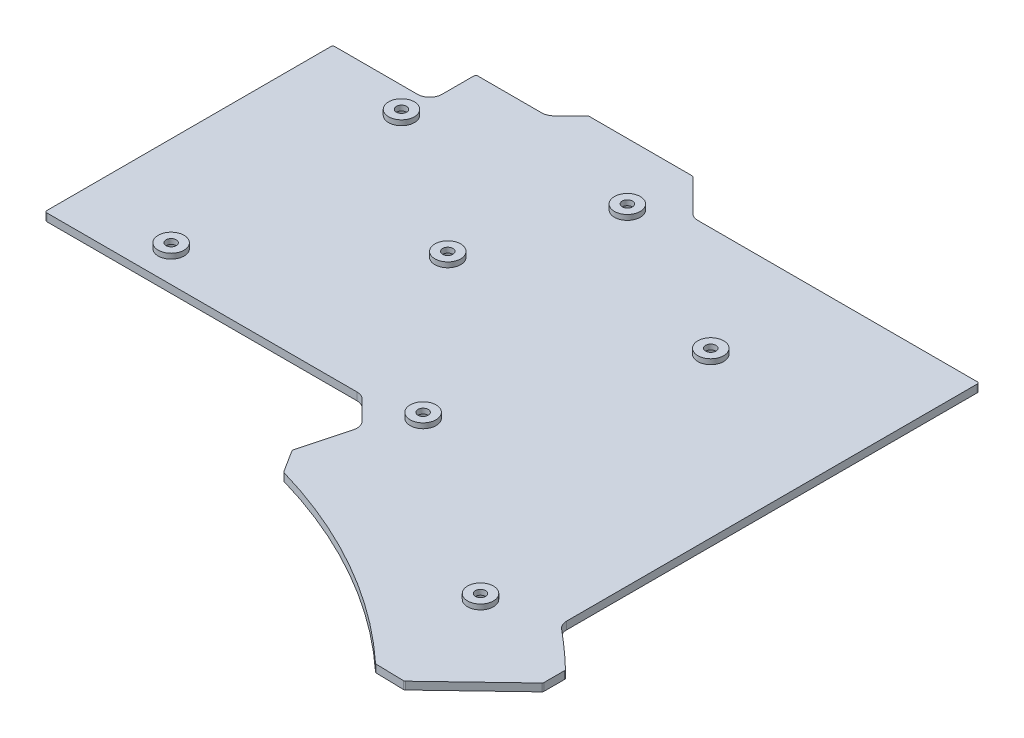
SolidWorks part; units mm, degrees
ref_plane "Piano frontale" through (0, 0, 0) normal (0, 0, 1) x (1, 0, 0)
ref_plane "Piano superiore" through (0, 0, 0) normal (0, 1, 0) x (1, 0, 0)
ref_plane "Piano destro" through (0, 0, 0) normal (1, 0, 0) x (0, 0, -1)
sketch "Schizzo1" plane through (0, 9.9972, 0) normal (0, -1, 0) x (1, 0, 0)
  line L17 (-61.586, 85.1099) -> (-61.586, 79.3099)
  line L18 (-61.586, 79.3099) -> (-48.9073, 79.3099)
  line L19 (-46.6445, 78.3726) -> (-43.5318, 75.2599)
  line L20 (-43.5318, 75.2599) -> (-22.9401, 75.2599)
  line L21 (-22.9401, 75.2599) -> (-16.8774, 81.3226)
  line L22 (-14.6146, 82.2599) -> (40.164, 82.2599)
  line L24 (40.164, 82.2599) -> (40.164, 162.6403)
  line L25 (48.3495, 171.436) -> (48.3495, 175.9915)
  line L26 (48.3495, 175.9915) -> (34.3416, 189.3477)
  line L27 (34.3416, 189.3477) -> (28.4404, 189.2072)
  line L28 (-13.0199, 165.7427) -> (-16.0073, 161.0261)
  line L29 (-16.0073, 161.0261) -> (-13.6027, 152.0521)
  line L30 (-14.4309, 148.9612) -> (-17.445, 145.9471)
  line L31 (-19.7077, 145.0099) -> (-80.536, 145.0099)
  line L32 (-80.536, 145.0099) -> (-80.536, 88.3099)
  line L33 (-80.536, 88.3099) -> (-64.786, 88.3099)
  line L34 (-61.586, 85.1099) -> (-61.586, 79.3099)
  line L35 (-61.586, 79.3099) -> (-48.9073, 79.3099)
  line L36 (-46.6445, 78.3726) -> (-43.5318, 75.2599)
  line L37 (-43.5318, 75.2599) -> (-22.9401, 75.2599)
  line L38 (-22.9401, 75.2599) -> (-16.8774, 81.3226)
  line L39 (-14.6146, 82.2599) -> (40.164, 82.2599)
  line L41 (40.164, 82.2599) -> (40.164, 162.6403)
  line L42 (48.3495, 171.436) -> (48.3495, 175.9915)
  line L43 (48.3495, 175.9915) -> (34.3416, 189.3477)
  line L44 (34.3416, 189.3477) -> (28.4404, 189.2072)
  line L45 (-13.0199, 165.7427) -> (-16.0073, 161.0261)
  line L46 (-16.0073, 161.0261) -> (-13.6027, 152.0521)
  line L47 (-14.4309, 148.9612) -> (-17.445, 145.9471)
  line L48 (-19.7077, 145.0099) -> (-80.536, 145.0099)
  line L49 (-80.536, 145.0099) -> (-80.536, 88.3099)
  line L50 (-80.536, 88.3099) -> (-64.786, 88.3099)
  circle A0 centre (27.8778, 167.853) radius 2.525 construction
  circle A1 centre (-8.4006, 142.7956) radius 2.525 construction
  circle A2 centre (-61.736, 138.7099) radius 2.525 construction
  circle A3 centre (-61.811, 93.6099) radius 2.525 construction
  circle A4 centre (-33.236, 113.1349) radius 2.525 construction
  circle A5 centre (8.864, 103.8349) radius 2.525 construction
  circle A6 centre (-23.711, 87.5599) radius 2.525 construction
  circle A7 centre (-23.711, 87.5599) radius 0.6 construction
  arc A8 (-61.586, 85.1099) -> (-64.786, 88.3099) centre (-64.786, 85.1099) ccw
  arc A9 (-46.6445, 78.3726) -> (-48.9073, 79.3099) centre (-48.9073, 76.1099) ccw
  arc A10 (-14.6146, 82.2599) -> (-16.8774, 81.3226) centre (-14.6146, 79.0599) ccw
  arc A11 (41.3114, 165.0952) -> (40.164, 162.6403) centre (43.364, 162.6403) ccw
  arc A12 (41.3114, 165.0952) -> (48.3495, 171.436) centre (-40.9879, 263.5214) ccw
  arc A13 (-13.0199, 165.7427) -> (28.4404, 189.2072) centre (-40.9879, 263.5214) ccw
  arc A14 (-14.4309, 148.9612) -> (-13.6027, 152.0521) centre (-16.6937, 151.2239) ccw
  arc A15 (-19.7077, 145.0099) -> (-17.445, 145.9471) centre (-19.7077, 148.2099) ccw
  arc A16 (-61.586, 85.1099) -> (-64.786, 88.3099) centre (-64.786, 85.1099) ccw
  arc A17 (-46.6445, 78.3726) -> (-48.9073, 79.3099) centre (-48.9073, 76.1099) ccw
  arc A18 (-14.6146, 82.2599) -> (-16.8774, 81.3226) centre (-14.6146, 79.0599) ccw
  arc A19 (41.3114, 165.0952) -> (40.164, 162.6403) centre (43.364, 162.6403) ccw
  arc A20 (41.3114, 165.0952) -> (48.3495, 171.436) centre (-40.9879, 263.5214) ccw
  arc A21 (-13.0199, 165.7427) -> (28.4404, 189.2072) centre (-40.9879, 263.5214) ccw
  arc A22 (-14.4309, 148.9612) -> (-13.6027, 152.0521) centre (-16.6937, 151.2239) ccw
  arc A23 (-19.7077, 145.0099) -> (-17.445, 145.9471) centre (-19.7077, 148.2099) ccw
  circle A24 centre (-33.236, 113.1349) radius 0.6 construction
  circle A25 centre (8.864, 103.8349) radius 0.6 construction
  circle A26 centre (27.8778, 167.853) radius 0.6 construction
  circle A27 centre (-61.811, 93.6099) radius 0.6 construction
  circle A28 centre (-61.736, 138.7099) radius 0.6 construction
  circle A29 centre (-8.4006, 142.7956) radius 0.6 construction
  circle A30 centre (27.8778, 167.853) radius 2.525
  circle A31 centre (-8.4006, 142.7956) radius 2.525
  circle A32 centre (-61.736, 138.7099) radius 2.525
  circle A33 centre (-61.811, 93.6099) radius 2.525
  circle A34 centre (-33.236, 113.1349) radius 2.525
  circle A35 centre (8.864, 103.8349) radius 2.525
  circle A36 centre (-23.711, 87.5599) radius 2.525
  circle A37 centre (-23.711, 87.5599) radius 0.6
  circle A38 centre (-33.236, 113.1349) radius 0.6
  circle A39 centre (8.864, 103.8349) radius 0.6
  circle A40 centre (27.8778, 167.853) radius 0.6
  circle A41 centre (-61.811, 93.6099) radius 0.6
  circle A42 centre (-61.736, 138.7099) radius 0.6
  circle A43 centre (-8.4006, 142.7956) radius 0.6
  dimension "D1" = 0
extrude "Estrusione-Estrusione1" add sketch "Schizzo1" against normal blind 1 contours A31 A43 | A34 A38 | A33 A41 | A36 A37 | A35 A39 | A32 A42 | A30 A40 region at (25.4243, 9.9972, 167.853) region at (-10.8542, 9.9972, 142.7956) region at (-64.1895, 9.9972, 138.7099) region at (-64.2645, 9.9972, 93.6099) region at (-35.6895, 9.9972, 113.1349) region at (6.4105, 9.9972, 103.8349) region at (-26.1645, 9.9972, 87.5599)
extrude "Estrusione-Estrusione3" add sketch "Schizzo1<4>" along normal offset from surface (1.5 mm away) 0.1 separate body contours A36 A35 A34 A33 A32 A31 A30 | A32 A42 | A31 A43 | A35 A39 | A34 A38 | A36 A37 | A33 A41 | A30 A40 region at (-12.3087, 9.9972, 122.9281) region at (25.4243, 9.9972, 167.853) region at (-10.8542, 9.9972, 142.7956) region at (-64.1895, 9.9972, 138.7099) region at (-64.2645, 9.9972, 93.6099) region at (-35.6895, 9.9972, 113.1349) region at (6.4105, 9.9972, 103.8349) region at (-26.1645, 9.9972, 87.5599)
sketch "Schizzo1<4>" plane through (0, 9.9972, 0) normal (0, -1, 0) x (1, 0, 0) same geometry as "Schizzo1"
sketch "Schizzo2" plane through (0, 8.4972, 0) normal (0, -1, 0) x (1, 0, 0)
  circle A0 centre (-61.736, 138.7099) radius 1
  circle A1 centre (-61.811, 93.6099) radius 1
  circle A2 centre (-23.711, 87.5599) radius 1
  circle A3 centre (-33.236, 113.1349) radius 1
  circle A4 centre (8.864, 103.8349) radius 1
  circle A5 centre (-8.4006, 142.7956) radius 1
  circle A6 centre (27.8778, 167.853) radius 1
  circle A7 centre (-61.736, 138.7099) radius 2.1
  circle A8 centre (-8.4006, 142.7956) radius 2.1
  circle A9 centre (27.8778, 167.853) radius 2.1
  circle A10 centre (8.864, 103.8349) radius 2.1
  circle A11 centre (-23.711, 87.5599) radius 2.1
  circle A12 centre (-61.811, 93.6099) radius 2.1
  circle A13 centre (-33.236, 113.1349) radius 2.1
  circle M1 centre (8.864, 103.8349) radius 0.6
  circle M2 centre (-33.236, 113.1349) radius 0.6
  circle M3 centre (-61.811, 93.6099) radius 0.6
  circle M4 centre (-61.736, 138.7099) radius 0.6
  circle M5 centre (-8.4006, 142.7956) radius 0.6
  circle M6 centre (27.8778, 167.853) radius 0.6
  circle M7 centre (-23.711, 87.5599) radius 0.6
  dimension "D1" = 2
  dimension "D2" = 4.2
extrude "Taglio-Estrusione1" cut sketch "Schizzo2" against normal through all contours A0 M4 | A5 M5 | A3 M2 | A1 M3 | A2 M7 | A4 M1 | A6 M6 region at (-62.7077, 8.4972, 138.7099) region at (-62.7827, 8.4972, 93.6099) region at (-24.6827, 8.4972, 87.5599) region at (-34.2077, 8.4972, 113.1349) region at (7.8923, 8.4972, 103.8349) region at (-9.3723, 8.4972, 142.7956) region at (26.9061, 8.4972, 167.853)
extrude "Taglio-Estrusione2" cut sketch "Schizzo2<3>" against normal blind 1.5 contours A11 | A13 | A7 | A12 | A10 | A8 | A9
sketch "Schizzo2<3>" plane through (0, 8.4972, 0) normal (0, -1, 0) x (1, 0, 0) same geometry as "Schizzo2"
sketch "Schizzo3" plane through (0, 8.4972, 0) normal (0, -1, 0) x (1, 0, 0)
  line L16 (-19.7077, 145.0099) -> (-80.536, 145.0099)
  line L17 (-80.536, 145.0099) -> (-80.536, 88.3099)
  line L18 (-80.536, 88.3099) -> (-64.786, 88.3099)
  line L19 (-61.586, 85.1099) -> (-61.586, 79.3099)
  line L20 (-61.586, 79.3099) -> (-48.9073, 79.3099)
  line L21 (-46.6445, 78.3726) -> (-43.5318, 75.2599)
  line L22 (-43.5318, 75.2599) -> (-22.9401, 75.2599)
  line L23 (-22.9401, 75.2599) -> (-16.8774, 81.3226)
  line L24 (-14.6146, 82.2599) -> (40.164, 82.2599)
  line L25 (40.164, 82.2599) -> (40.164, 162.6403)
  line L26 (48.3495, 171.436) -> (48.3495, 175.9915)
  line L27 (48.3495, 175.9915) -> (34.3416, 189.3477)
  line L28 (34.3416, 189.3477) -> (28.4404, 189.2072)
  line L29 (-13.0199, 165.7427) -> (-16.0073, 161.0261)
  line L30 (-16.0073, 161.0261) -> (-13.6027, 152.0521)
  line L31 (-14.4309, 148.9612) -> (-17.445, 145.9471)
  line L32 (-19.7077, 145.0099) -> (-80.536, 145.0099)
  line L33 (-80.536, 145.0099) -> (-80.536, 88.3099)
  line L34 (-80.536, 88.3099) -> (-64.786, 88.3099)
  line L35 (-61.586, 85.1099) -> (-61.586, 79.3099)
  line L36 (-61.586, 79.3099) -> (-48.9073, 79.3099)
  line L37 (-46.6445, 78.3726) -> (-43.5318, 75.2599)
  line L38 (-43.5318, 75.2599) -> (-22.9401, 75.2599)
  line L39 (-22.9401, 75.2599) -> (-16.8774, 81.3226)
  line L40 (-14.6146, 82.2599) -> (40.164, 82.2599)
  line L41 (40.164, 82.2599) -> (40.164, 162.6403)
  line L42 (48.3495, 171.436) -> (48.3495, 175.9915)
  line L43 (48.3495, 175.9915) -> (34.3416, 189.3477)
  line L44 (34.3416, 189.3477) -> (28.4404, 189.2072)
  line L45 (-13.0199, 165.7427) -> (-16.0073, 161.0261)
  line L46 (-16.0073, 161.0261) -> (-13.6027, 152.0521)
  line L47 (-14.4309, 148.9612) -> (-17.445, 145.9471)
  line L64 (-19.7077, 144.8099) -> (-80.336, 144.8099)
  line L65 (-80.336, 144.8099) -> (-80.336, 88.5099)
  line L66 (-80.336, 88.5099) -> (-64.786, 88.5099)
  line L67 (-61.386, 85.1099) -> (-61.386, 79.5099)
  line L68 (-61.386, 79.5099) -> (-48.9073, 79.5099)
  line L69 (-46.5031, 78.514) -> (-43.449, 75.4599)
  line L70 (-43.449, 75.4599) -> (-23.023, 75.4599)
  line L71 (-23.023, 75.4599) -> (-17.0188, 81.464)
  line L72 (-14.6146, 82.4599) -> (39.964, 82.4599)
  line L73 (39.964, 82.4599) -> (39.964, 162.6403)
  line L74 (48.1495, 171.5207) -> (48.1495, 175.9059)
  line L75 (48.1495, 175.9059) -> (34.2635, 189.1458)
  line L76 (34.2635, 189.1458) -> (28.5213, 189.0091)
  line L77 (-12.8917, 165.5713) -> (-15.7914, 160.9931)
  line L78 (-15.7914, 160.9931) -> (-13.4095, 152.1039)
  line L79 (-14.2895, 148.8198) -> (-17.3036, 145.8057)
  line L80 (-19.2935, 144.8099) -> (-80.336, 144.8099)
  line L81 (-80.336, 144.8099) -> (-80.336, 88.5099)
  line L82 (-80.336, 88.5099) -> (-63.786, 88.5099)
  line L83 (-61.386, 86.1099) -> (-61.386, 79.5099)
  line L84 (-61.386, 79.5099) -> (-48.4931, 79.5099)
  line L85 (-46.796, 78.8069) -> (-43.449, 75.4599)
  line L86 (-43.449, 75.4599) -> (-23.023, 75.4599)
  line L87 (-23.023, 75.4599) -> (-16.7259, 81.7569)
  line L88 (-15.0289, 82.4599) -> (39.964, 82.4599)
  line L89 (39.964, 82.4599) -> (39.964, 163.1087)
  line L90 (48.1495, 171.5207) -> (48.1495, 175.9059)
  line L91 (48.1495, 175.9059) -> (34.2635, 189.1458)
  line L92 (34.2635, 189.1458) -> (28.5213, 189.0091)
  line L93 (-12.8917, 165.5713) -> (-15.7914, 160.9931)
  line L94 (-15.7914, 160.9931) -> (-13.2601, 151.5462)
  line L95 (-13.8813, 149.228) -> (-17.5965, 145.5128)
  arc A8 (-19.7077, 145.0099) -> (-17.445, 145.9471) centre (-19.7077, 148.2099) ccw
  arc A9 (-61.586, 85.1099) -> (-64.786, 88.3099) centre (-64.786, 85.1099) ccw
  arc A10 (-46.6445, 78.3726) -> (-48.9073, 79.3099) centre (-48.9073, 76.1099) ccw
  arc A11 (-14.6146, 82.2599) -> (-16.8774, 81.3226) centre (-14.6146, 79.0599) ccw
  arc A12 (41.3114, 165.0952) -> (40.164, 162.6403) centre (43.364, 162.6403) ccw
  arc A13 (41.3114, 165.0952) -> (48.3495, 171.436) centre (-40.9879, 263.5214) ccw
  arc A14 (-13.0199, 165.7427) -> (28.4404, 189.2072) centre (-40.9879, 263.5214) ccw
  arc A15 (-14.4309, 148.9612) -> (-13.6027, 152.0521) centre (-16.6937, 151.2239) ccw
  arc A16 (-19.7077, 145.0099) -> (-17.445, 145.9471) centre (-19.7077, 148.2099) ccw
  arc A17 (-61.586, 85.1099) -> (-64.786, 88.3099) centre (-64.786, 85.1099) ccw
  arc A18 (-46.6445, 78.3726) -> (-48.9073, 79.3099) centre (-48.9073, 76.1099) ccw
  arc A19 (-14.6146, 82.2599) -> (-16.8774, 81.3226) centre (-14.6146, 79.0599) ccw
  arc A20 (41.3114, 165.0952) -> (40.164, 162.6403) centre (43.364, 162.6403) ccw
  arc A21 (41.3114, 165.0952) -> (48.3495, 171.436) centre (-40.9879, 263.5214) ccw
  arc A22 (-13.0199, 165.7427) -> (28.4404, 189.2072) centre (-40.9879, 263.5214) ccw
  arc A23 (-14.4309, 148.9612) -> (-13.6027, 152.0521) centre (-16.6937, 151.2239) ccw
  arc A24 (39.964, 163.1087) -> (40.8311, 164.9554) centre (42.364, 163.1087) cw
  arc A25 (-16.7259, 81.7569) -> (-15.0289, 82.4599) centre (-15.0289, 80.0599) cw
  arc A26 (-48.4931, 79.5099) -> (-46.796, 78.8069) centre (-48.4931, 77.1099) cw
  arc A27 (-63.786, 88.5099) -> (-61.386, 86.1099) centre (-63.786, 86.1099) cw
  arc A28 (-17.5965, 145.5128) -> (-19.2935, 144.8099) centre (-19.2935, 147.2099) cw
  arc A29 (-13.8813, 149.228) -> (-13.2601, 151.5462) centre (-15.5783, 150.9251) ccw
  arc A32 (-19.7077, 144.8099) -> (-17.3036, 145.8057) centre (-19.7077, 148.2099) ccw
  arc A33 (-61.386, 85.1099) -> (-64.786, 88.5099) centre (-64.786, 85.1099) ccw
  arc A34 (-46.5031, 78.514) -> (-48.9073, 79.5099) centre (-48.9073, 76.1099) ccw
  arc A35 (-14.6146, 82.4599) -> (-17.0188, 81.464) centre (-14.6146, 79.0599) ccw
  arc A36 (41.1831, 165.2486) -> (39.964, 162.6403) centre (43.364, 162.6403) ccw
  arc A37 (41.1831, 165.2486) -> (48.1495, 171.5207) centre (-40.9879, 263.5214) ccw
  arc A38 (-12.8917, 165.5713) -> (28.5213, 189.0091) centre (-40.9879, 263.5214) ccw
  arc A39 (-14.2895, 148.8198) -> (-13.4095, 152.1039) centre (-16.6937, 151.2239) ccw
  arc A40 (-19.7077, 144.8099) -> (-17.3036, 145.8057) centre (-19.7077, 148.2099) ccw
  arc A41 (-61.386, 85.1099) -> (-64.786, 88.5099) centre (-64.786, 85.1099) ccw
  arc A42 (-46.5031, 78.514) -> (-48.9073, 79.5099) centre (-48.9073, 76.1099) ccw
  arc A43 (-14.6146, 82.4599) -> (-17.0188, 81.464) centre (-14.6146, 79.0599) ccw
  arc A44 (41.1831, 165.2486) -> (39.964, 162.6403) centre (43.364, 162.6403) ccw
  arc A45 (40.8311, 164.9554) -> (48.1495, 171.5207) centre (-40.9879, 263.5214) ccw
  arc A46 (-12.8917, 165.5713) -> (28.5213, 189.0091) centre (-40.9879, 263.5214) ccw
  arc A47 (-14.2895, 148.8198) -> (-13.4095, 152.1039) centre (-16.6937, 151.2239) ccw
  arc M56 (-17.445, 145.9471) -> (-19.7077, 145.0099) centre (-19.7077, 148.2099) cw
  line M57 (-19.7077, 145.0099) -> (-80.536, 145.0099)
  line M58 (-80.536, 145.0099) -> (-80.536, 88.3099)
  line M59 (-80.536, 88.3099) -> (-64.786, 88.3099)
  arc M60 (-64.786, 88.3099) -> (-61.586, 85.1099) centre (-64.786, 85.1099) cw
  line M61 (-61.586, 85.1099) -> (-61.586, 79.3099)
  line M62 (-61.586, 79.3099) -> (-48.9073, 79.3099)
  arc M63 (-48.9073, 79.3099) -> (-46.6445, 78.3726) centre (-48.9073, 76.1099) cw
  line M64 (-46.6445, 78.3726) -> (-43.5318, 75.2599)
  line M65 (-43.5318, 75.2599) -> (-22.9401, 75.2599)
  line M66 (-22.9401, 75.2599) -> (-16.8774, 81.3226)
  arc M67 (-16.8774, 81.3226) -> (-14.6146, 82.2599) centre (-14.6146, 79.0599) cw
  line M68 (-14.6146, 82.2599) -> (40.164, 82.2599)
  line M69 (40.164, 82.2599) -> (40.164, 162.6403)
  arc M70 (40.164, 162.6403) -> (41.3114, 165.0952) centre (43.364, 162.6403) cw
  arc M71 (41.3114, 165.0952) -> (48.3495, 171.436) centre (-40.9879, 263.5214) ccw
  line M72 (48.3495, 171.436) -> (48.3495, 175.9915)
  line M73 (48.3495, 175.9915) -> (34.3416, 189.3477)
  line M74 (34.3416, 189.3477) -> (28.4404, 189.2072)
  arc M75 (28.4404, 189.2072) -> (-13.0199, 165.7427) centre (-40.9879, 263.5214) cw
  line M76 (-13.0199, 165.7427) -> (-16.0073, 161.0261)
  line M77 (-16.0073, 161.0261) -> (-13.6027, 152.0521)
  arc M78 (-13.6027, 152.0521) -> (-14.4309, 148.9612) centre (-16.6937, 151.2239) cw
  line M79 (-14.4309, 148.9612) -> (-17.445, 145.9471)
  dimension "D3" = 2.4
  dimension "D1" = 0
  dimension "D2" = 0.2
extrude "Taglio-Estrusione3" cut sketch "Schizzo3" against normal through all contours L95 A47 L94 L93 A46 L92 L91 L90 A45 A44 L89 L88 A43 L87 L86 L85 A42 L84 L83 A41 L82 L81 L80 A40 M79 M56 M57 M58 M59 M60 M61 M62 M63 M64 M65 M66 M67 M68 M69 M70 M71 M72 M73 M74 M75 M76 M77 M78 | A45 A24 L89 A44 | A47 L95 A29 L94 | A40 L80 A28 L95 | A41 L83 A27 L82 | A42 L85 A26 L84 | A43 L88 A25 L87 region at (-18.4173, 8.4972, 145.0944) region at (-18.3967, 8.4972, 145.0446) region at (-13.3761, 8.4972, 150.335) region at (-62.3672, 8.4972, 87.5286) region at (-48.7002, 8.4972, 79.5073) region at (-16.8705, 8.4972, 81.6086) region at (40.2578, 8.4972, 164.092)
fillet "Raccordo1" radius 0.4 12 edges at (-15.7914, 9.2472, 160.9931) (-12.8917, 9.2472, 165.5713) (28.5213, 9.2472, 189.0091) (48.1495, 9.2472, 171.5207) (48.1495, 9.2472, 175.9059) (34.2635, 9.2472, 189.1458) (39.964, 9.2472, 82.4599) (-23.023, 9.2472, 75.4599) (-43.449, 9.2472, 75.4599) (-61.386, 9.2472, 79.5099) (-80.336, 9.2472, 88.5099) (-80.336, 9.2472, 144.8099)
